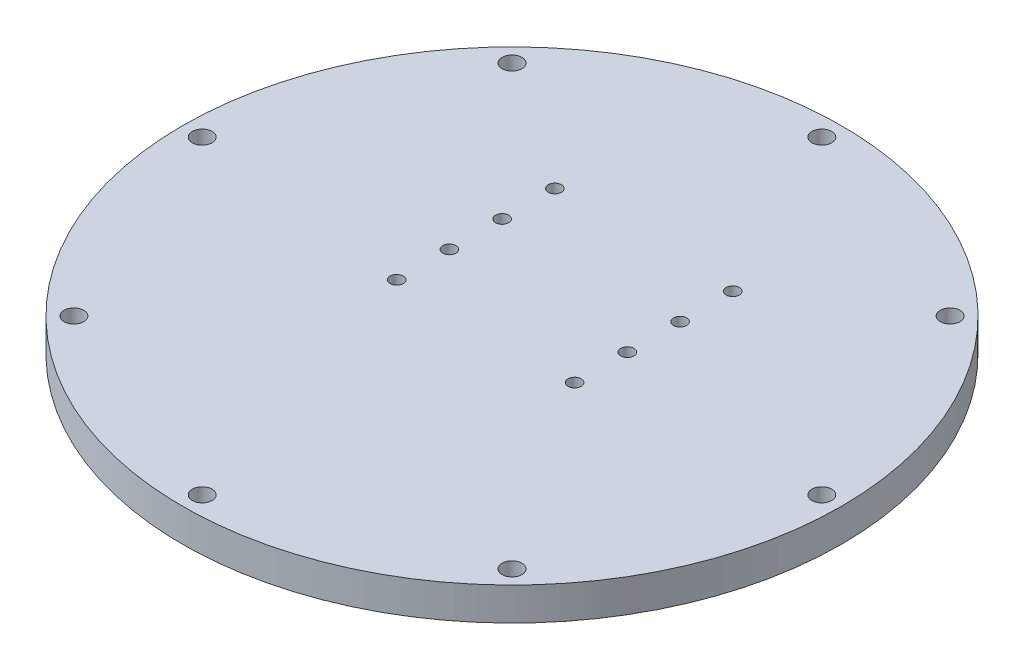
SolidWorks part; units mm, degrees
ref_plane "Front Plane" through (0, 0, 0) normal (0, 0, 1) x (1, 0, 0)
ref_plane "Top Plane" through (0, 0, 0) normal (0, 1, 0) x (1, 0, 0)
ref_plane "Right Plane" through (0, 0, 0) normal (1, 0, 0) x (0, 0, -1)
sketch "Sketch2" plane through (0, 0, 0) normal (0, 0, 1) x (1, 0, 0)
  line L0 (0, 5) -> (0, 0)
  line L1 (0, 0) -> (50, 0)
  line L2 (50, 0) -> (50, 5)
  line L3 (50, 5) -> (41, 5)
  line L4 (41, 5) -> (41, 58) construction
  line L5 (41, 58) -> (38, 58) construction
  line L6 (38, 58) -> (38, 5) construction
  line L7 (38, 5) -> (0, 5)
  line L8 (0, 0) -> (0, 38.6828) construction
  line L9 (38, 5) -> (41, 5)
  dimension "D1" = 50
  dimension "D2" = 5
  dimension "D3" = 58
  dimension "D4" = 9
  dimension "D5" = 3
revolve "Revolve1" add sketch "Sketch2" angle 360 about L8
sketch "Sketch3" plane through (0, 0, 0) normal (0, 1, 0) x (1, 0, 0)
  line L0 (-13.5, 12) -> (-13.5, 4) construction
  line L1 (13.5, 12) -> (13.5, 4) construction
  line L2 (-13.5, 12) -> (-13.5, 20) construction
  line L3 (0, 0) -> (0, -47) construction
  circle A0 centre (-13.5, 12) radius 1
  circle A1 centre (13.5, 12) radius 1
  circle A2 centre (-13.5, 4) radius 1
  circle A3 centre (-13.5, -4) radius 1
  circle A4 centre (13.5, 4) radius 1
  circle A5 centre (13.5, -4) radius 1
  circle A6 centre (-13.5, 20) radius 1
  circle A7 centre (13.5, 20) radius 1
  circle A8 centre (0, -47) radius 1.5
  circle A9 centre (0, 0) radius 47 construction
  circle A10 centre (-33.234, -33.234) radius 1.5
  circle A11 centre (-47, 0) radius 1.5
  circle A12 centre (-33.234, 33.234) radius 1.5
  circle A13 centre (0, 47) radius 1.5
  circle A14 centre (33.234, 33.234) radius 1.5
  circle A15 centre (47, 0) radius 1.5
  circle A16 centre (33.234, -33.234) radius 1.5
  circle A18 centre (0, 26.5) radius 12.5 construction
  circle A19 centre (0, -11) radius 25 construction
  point P25 (0, 0)
  dimension "D1" = 2
  dimension "D11" = 3
  dimension "D12" = 94
  dimension "D14" = 50
  dimension "D15" = 25
  dimension "D2" = 27
  dimension "D3" = 13.5
  dimension "D4" = 12
  dimension "D6" = 8
  dimension "D8" = 8
  dimension "D10" = 8
  dimension "D16" = 6.5
  dimension "D5" = 3
  dimension "D7" = 3
  dimension "D9" = 2
  dimension "D13" = 8
extrude "Cut-Extrude1" cut sketch "Sketch3" along normal through all
sketch "Sketch5" plane through (0, 0, 0) normal (0, -1, 0) x (-1, 0, 0)
  circle A5 centre (13.5, -4) radius 3
  circle A6 centre (13.5, -4) radius 3
  circle A11 centre (13.5, 4) radius 3
  circle A12 centre (13.5, 4) radius 3
  circle A14 centre (13.5, 12) radius 3
  circle A15 centre (13.5, 12) radius 3
  circle A17 centre (13.5, 20) radius 3
  circle A18 centre (13.5, 20) radius 3
  circle A20 centre (-13.5, -4) radius 3
  circle A21 centre (-13.5, -4) radius 3
  circle A23 centre (-13.5, 4) radius 3
  circle A24 centre (-13.5, 4) radius 3
  circle A26 centre (-13.5, 12) radius 3
  circle A27 centre (-13.5, 12) radius 3
  circle A29 centre (-13.5, 20) radius 3
  circle A30 centre (-13.5, 20) radius 3
  dimension "D1" = 2
  dimension "D2" = 2
  dimension "D3" = 2
  dimension "D4" = 2
  dimension "D5" = 2
  dimension "D6" = 2
  dimension "D7" = 2
  dimension "D8" = 2
extrude "Cut-Extrude2" cut sketch "Sketch5" against normal blind 2
